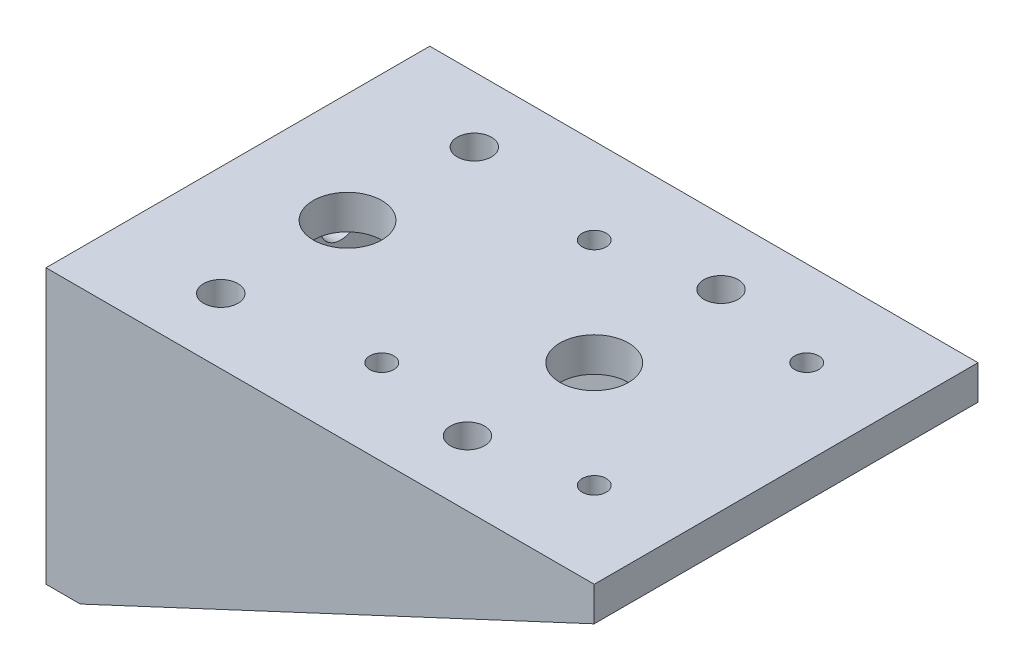
SolidWorks part; units mm, degrees
ref_plane "Спереди" through (0, 0, 0) normal (0, 0, 1) x (1, 0, 0)
ref_plane "Сверху" through (0, 0, 0) normal (0, 1, 0) x (1, 0, 0)
ref_plane "Справа" through (0, 0, 0) normal (1, 0, 0) x (0, 0, -1)
sketch "Эскиз1" plane through (0, 0, 0) normal (0, 1, 0) x (1, 0, 0)
  line L0 (0, 28) -> (80, 28) construction
  line L1 (0, 0) -> (80, 0)
  line L2 (0, 0) -> (0, 56)
  line L3 (0, 56) -> (80, 56)
  line L4 (80, 0) -> (80, 56)
  line L5 (52, 46.5) -> (52, 9.5) construction
  line L6 (30, 56) -> (30, 0) construction
  line L7 (16, 46.5) -> (16, 9.5) construction
  circle A0 centre (16, 46.5) radius 2.5
  circle A1 centre (16, 9.5) radius 2.5
  circle A2 centre (52, 46.5) radius 2.5
  circle A3 centre (52, 9.5) radius 2.5
  circle A4 centre (52, 28) radius 5
  circle A5 centre (67.5, 12.5) radius 1.75
  circle A6 centre (67.5, 43.5) radius 1.75
  circle A7 centre (36.5, 43.5) radius 1.75
  circle A8 centre (36.5, 12.5) radius 1.75
  circle A9 centre (16, 28) radius 5
  dimension "D1" = 80
  dimension "D2" = 56
extrude "Бобышка-Вытянуть1" add sketch "Эскиз1" along normal blind 5
sketch "Эскиз2" plane through (0, 0, 0) normal (0, -1, 0) x (-1, 0, 0)
  line L0 (-80, 0) -> (0, 0)
  line L1 (0, 0) -> (0, 56)
  line L2 (0, 56) -> (-80, 56)
  line L3 (-80, 56) -> (-80, 51)
  line L4 (-80, 0) -> (-80, 56) construction
  line L5 (-80, 51) -> (-5, 51)
  line L6 (-5, 51) -> (-5, 5)
  line L7 (-5, 5) -> (-80, 5)
  line L8 (-80, 5) -> (-80, 0)
  dimension "D1" = 5
  dimension "D2" = 5
  dimension "D3" = 5
extrude "Бобышка-Вытянуть2" add sketch "Эскиз2" along normal blind 35
sketch "Эскиз3" plane through (0, 0, 0) normal (0, 0, 1) x (1, 0, 0)
  line L0 (5, -35) -> (80, 0)
  line L1 (80, -35) -> (0, -35) construction
  line L2 (80, 5) -> (80, -35) construction
  line L3 (80, 0) -> (80, -35)
  line L4 (80, -35) -> (5, -35)
  dimension "D1" = 5
  dimension "D2" = 5
extrude "Вырез-Вытянуть1" cut sketch "Эскиз3" against normal up to surface (56 mm away) up to face at (40, -15, -56)
sketch "Эскиз4" plane through (0, 0, 0) normal (-1, 0, 0) x (0, 0, 1)
  line L0 (-28, -38) -> (-28, 5) construction
  line L3 (0, -15) -> (-56, -15) construction
  line L6 (-56, 5) -> (0, 5) construction
  circle A0 centre (-18, -25) radius 3
  circle A1 centre (-18, -5) radius 3
  circle A2 centre (-38, -5) radius 3
  circle A3 centre (-38, -25) radius 3
  dimension "D1" = 6
  dimension "D2" = 20
  dimension "D3" = 20
  dimension "D4" = 20
extrude "Вырез-Вытянуть2" cut sketch "Эскиз4" against normal up to surface (5 mm away) up to face at (5, -17.5, -28)
